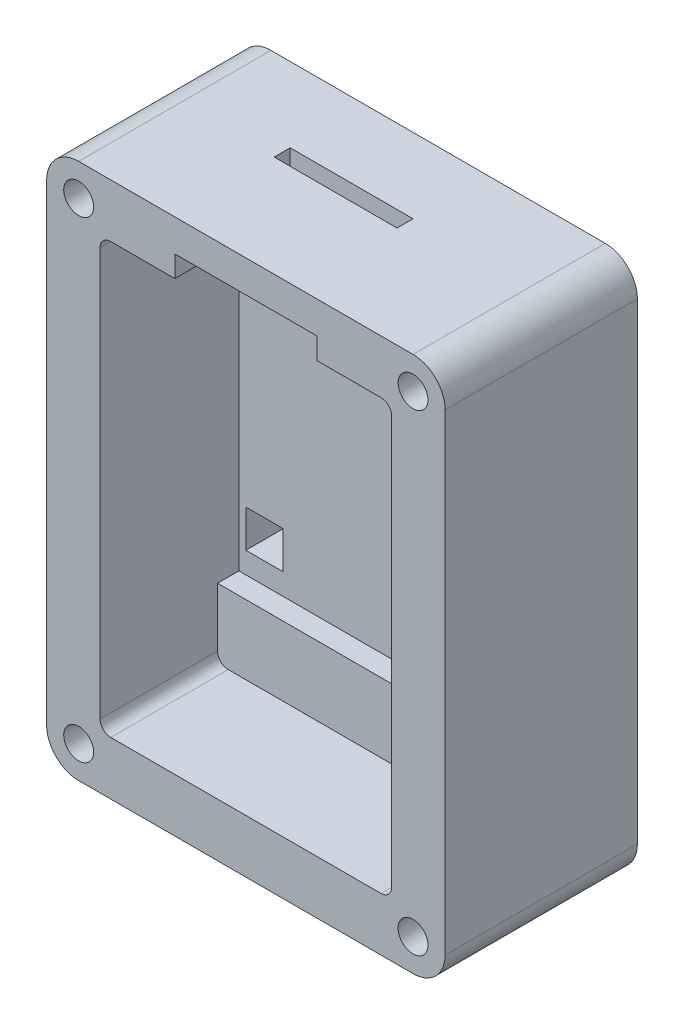
SolidWorks part; units mm, degrees
note: The reader was unsure of these and kept them because the rebuilt part matched: shared geometry of "스케치1<2>".
ref_plane "정면" through (0, 0, 0) normal (0, 0, 1) x (1, 0, 0)
ref_plane "윗면" through (0, 0, 0) normal (0, 1, 0) x (1, 0, 0)
ref_plane "우측면" through (0, 0, 0) normal (1, 0, 0) x (0, 0, -1)
sketch "스케치1" plane through (0, 0, 0) normal (0, 0, 1) x (1, 0, 0)
  line L5 (-13.65, -20.1) -> (13.65, -20.1)
  line L6 (-13.65, -20.1) -> (-13.65, 20.1)
  line L7 (-13.65, 20.1) -> (13.65, 20.1)
  line L8 (13.65, -20.1) -> (13.65, 20.1)
  line L9 (-13.65, -20.1) -> (13.65, 20.1) construction
  line L10 (-13.65, 20.1) -> (13.65, -20.1) construction
  line L11 (-18.65, -25.1) -> (18.65, -25.1)
  line L12 (-18.65, -25.1) -> (-18.65, 25.1)
  line L13 (-18.65, 25.1) -> (18.65, 25.1)
  line L14 (18.65, -25.1) -> (18.65, 25.1)
  line L15 (-18.65, -25.1) -> (18.65, 25.1) construction
  line L16 (-18.65, 25.1) -> (18.65, -25.1) construction
  point P0 (0, 0)
  point P7 (0, 0)
  dimension "D1" = 40.2
  dimension "D2" = 27.3
  dimension "D3" = 5
  dimension "D4" = 5
extrude "보스-돌출1" add sketch "스케치1" along normal blind 18
extrude "보스-돌출2" add sketch "스케치1<2>" along normal blind 2 contours L5 L8 L7 L6
sketch "스케치1<2>" plane through (0, 0, 0) normal (0, 0, 1) x (1, 0, 0) same geometry as "스케치1"
sketch "스케치2" plane through (0, 0, 0) normal (0, 0, 1) x (1, 0, 0)
  line L0 (0, 11.9) -> (0, 0) construction
  line L5 (-13.65, -20.1) -> (13.65, -20.1) construction
  circle A0 centre (0, 11.9) radius 4.2
  dimension "D1" = 8.4
  dimension "D2" = 32
extrude "컷-돌출2" cut sketch "스케치2" along normal through all
sketch "스케치3" plane through (0, 0, 2) normal (0, 0, 1) x (1, 0, 0)
  line L1 (-9.5, -11.6) -> (-13, -11.6)
  line L2 (-9.5, -11.6) -> (-9.5, -8.1)
  line L3 (-9.5, -8.1) -> (-13, -8.1)
  line L4 (-13, -11.6) -> (-13, -8.1)
  line L5 (-9.5, -11.6) -> (-13, -8.1) construction
  line L6 (-9.5, -8.1) -> (-13, -11.6) construction
  line L7 (-13.65, -20.1) -> (13.65, -20.1) construction
  line L8 (-13.65, -20.1) -> (-13.65, 20.1) construction
  point P0 (-11.25, -9.85)
  dimension "D1" = 3.5
  dimension "D2" = 3.5
  dimension "D3" = 8.5
  dimension "D4" = 0.65
extrude "컷-돌출3" cut sketch "스케치3" against normal through all
sketch "스케치4" plane through (0, 0, 2) normal (0, 0, 1) x (1, 0, 0)
  line L0 (-13.65, -20.1) -> (13.65, -20.1)
  line L1 (13.65, -20.1) -> (13.65, 20.1)
  line L2 (13.65, -20.1) -> (13.65, 20.1) construction
  line L3 (13.65, 20.1) -> (4.25, 20.1)
  line L4 (4.25, 16.6) -> (4.25, 7.4)
  line L5 (4.25, 7.4) -> (-4.25, 7.4)
  line L6 (-4.25, 7.4) -> (-4.25, 16.6)
  line L7 (-4.25, 20.1) -> (-13.65, 20.1)
  line L8 (-13.65, 20.1) -> (-13.65, -20.1) construction
  line L9 (-13.65, 20.1) -> (-13.65, -20.1)
  line L10 (0, 7.4) -> (0, 0) construction
  line L11 (-13, -11.6) -> (-9.5, -11.6)
  line L12 (-13, -11.6) -> (-13, -8.1)
  line L13 (-13, -8.1) -> (-9.5, -8.1)
  line L14 (-9.5, -11.6) -> (-9.5, -8.1)
  line L15 (13.65, 20.1) -> (-13.65, 20.1) construction
  line L16 (-4.25, 20.1) -> (4.25, 20.1)
  line L17 (-4.25, 16.6) -> (4.25, 16.6)
  dimension "D1" = 27.5
  dimension "D2" = 8.5
  dimension "D3" = 3.5
extrude "보스-돌출3" add sketch "스케치4" along normal blind 3
sketch "스케치5" plane through (0, 0, 5) normal (0, 0, 1) x (1, 0, 0)
  line L0 (-13.65, 20.1) -> (-13.65, -20.1) construction
  line L1 (13.65, -20.1) -> (-13.65, -20.1)
  line L2 (13.65, -20.1) -> (13.65, -13.6)
  line L3 (13.65, -13.6) -> (-13.65, -13.6)
  line L4 (-13.65, -20.1) -> (-13.65, -13.6)
  dimension "D1" = 6.5
extrude "보스-돌출4" add sketch "스케치5" along normal blind 2
sketch "스케치6" plane through (0, 25.1, 0) normal (0, 1, 0) x (1, 0, 0)
  line L0 (13.65, -7) -> (-13.65, -7) construction
  line L1 (-6.85, -7) -> (4.65, -7)
  line L2 (-6.85, -7) -> (-6.85, -8.5)
  line L3 (-6.85, -8.5) -> (4.65, -8.5)
  line L4 (4.65, -7) -> (4.65, -8.5)
  line L5 (-13.65, -18) -> (-13.65, -5) construction
  dimension "D1" = 18.3
  dimension "D2" = 11.5
  dimension "D3" = 1.5
extrude "컷-돌출4" cut sketch "스케치6" against normal blind 10
fillet "필렛1" radius 1 4 edges at (13.65, -20.1, 12.5) (13.65, 20.1, 11.5) (-13.65, 20.1, 11.5) (-13.65, -20.1, 12.5)
fillet "필렛2" radius 3 4 edges at (18.65, -25.1, 9) (-18.65, -25.1, 9) (-18.65, 25.1, 9) (18.65, 25.1, 9)
sketch "스케치7" plane through (0, 0, 18) normal (0, 0, 1) x (1, 0, 0)
  circle A0 centre (-15.65, 22.1) radius 1.4
  circle A1 centre (15.65, 22.1) radius 1.4
  circle A2 centre (-15.65, -22.1) radius 1.4
  circle A3 centre (15.65, -22.1) radius 1.4
  dimension "D1" = 2.8
  dimension "D2" = 2.8
  dimension "D3" = 2.8
  dimension "D4" = 2.8
extrude "컷-돌출5" cut sketch "스케치7" against normal blind 10
sketch "스케치8" plane through (0, 0, 18) normal (0, 0, 1) x (1, 0, 0)
  line L0 (12.65, 20.1) -> (-12.65, 20.1) construction
  line L1 (-6.65, 18.1) -> (6.65, 18.1)
  line L2 (-6.65, 18.1) -> (-6.65, 22.1)
  line L3 (-6.65, 22.1) -> (6.65, 22.1)
  line L4 (6.65, 18.1) -> (6.65, 22.1)
  line L5 (-6.65, 18.1) -> (6.65, 22.1) construction
  line L6 (-6.65, 22.1) -> (6.65, 18.1) construction
  line L7 (-18.65, 22.1) -> (-18.65, -22.1) construction
  point P0 (0, 20.1)
  dimension "D1" = 12
  dimension "D2" = 2
extrude "컷-돌출6" cut sketch "스케치8" against normal up to surface (11 mm away) up to face at (-1.1, 22.6, 7)
